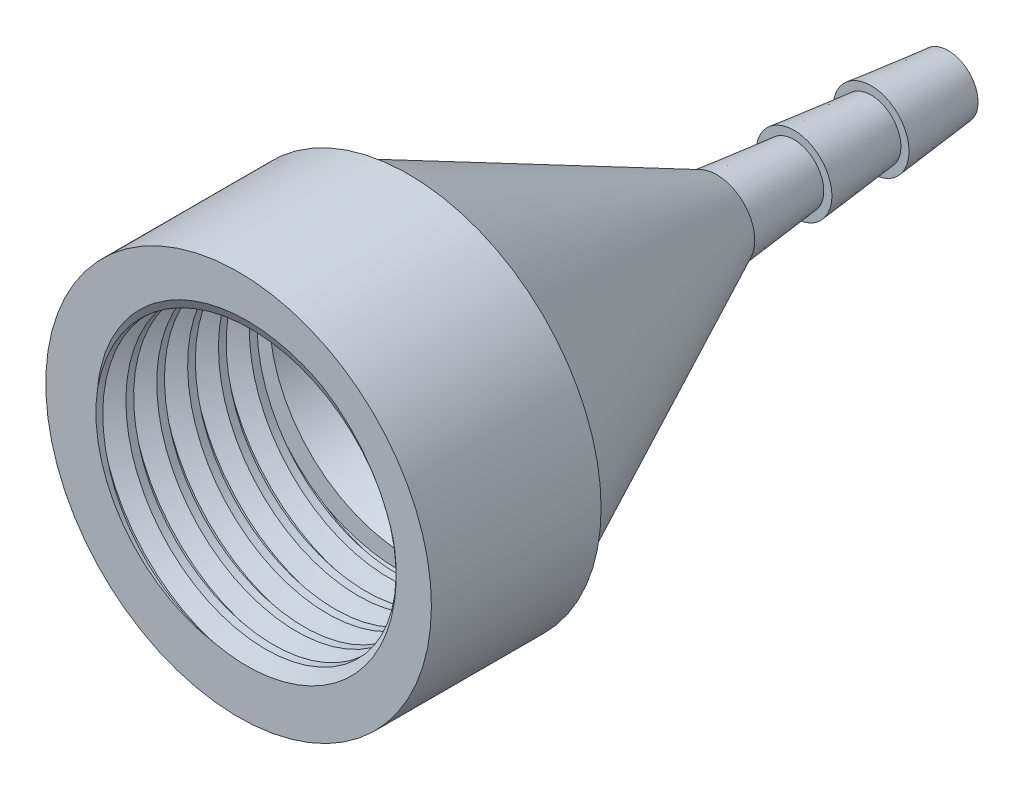
SolidWorks part; units mm, degrees
ref_plane "Front Plane" through (0, 0, 0) normal (0, 0, 1) x (1, 0, 0)
ref_plane "Top Plane" through (0, 0, 0) normal (0, 1, 0) x (1, 0, 0)
ref_plane "Right Plane" through (0, 0, 0) normal (1, 0, 0) x (0, 0, -1)
sketch "Sketch1" plane through (0, 0, 0) normal (0, 0, 1) x (1, 0, 0)
  circle A0 centre (0, 0) radius 12.5
  circle A1 centre (0, 0) radius 9.25
  dimension "D1" = 25
  dimension "D2" = 18.5
extrude "Boss-Extrude1" add sketch "Sketch1" along normal blind 11
thread "Thread1" pitch 2 method cut profile "Thread Profile1" start angle 0, offset 1.55, length 0, pitch 2, diameter 18.5
ref_plane "Plane1" through (-9.25, 0, 12.55) normal (0, -1, 0) x (-1, 0, 0)
sketch "Thread Profile1" plane through (-9.25, 0, 12.55) normal (0, -1, 0) x (-1, 0, 0)
  line L0 (0, 0) -> (0, 2) construction
  line L1 (0, 0) -> (1.0825, 0.625)
  line L2 (1.0825, 0.625) -> (1.0825, 0.875)
  line L3 (1.0825, 0.875) -> (0, 1.5)
  line L4 (1.0825, 0.75) -> (0, 0.75) construction
  line L11 (0, 0) -> (0, 1.5)
  point P2 (0, 0)
  dimension "Pitch" = 2
  dimension "Profile_Angle" = 60
  dimension "Profile_Land" = 0.25
  dimension "Profile_Height" = 1.0825
sketch "Sketch6" plane through (0, 0, 0) normal (0, 0, 1) x (1, 0, 0)
  circle A0 centre (0, 0) radius 12
extrude "Boss-Extrude2" add sketch "Sketch6" against normal blind 20 draft 25.5 separate body
sketch "Sketch13" plane through (0, 0, 0) normal (0, 0, -1) x (-1, 0, 0)
  circle A0 centre (0, 0) radius 9
extrude "Cut-Extrude1" cut sketch "Sketch13" along normal blind 20 draft 21.5
sketch "Sketch18" plane through (0, 0, -20) normal (0, 0, -1) x (-1, 0, 0)
  circle A0 centre (0, 0) radius 2.46
  dimension "D1" = 4.92
extrude "Boss-Extrude3" add sketch "Sketch18" along normal blind 5 draft 6
pattern_linear "LPattern1" count 3 spacing 5 along (0, 0, -1) of "Boss-Extrude3"
sketch "Sketch20" plane through (0, 0, -35) normal (0, 0, -1) x (-1, 0, 0)
  circle A0 centre (0, 0) radius 1
  dimension "D1" = 2
extrude "Cut-Extrude2" cut sketch "Sketch20" against normal through all
fillet "Fillet1" radius 10 1 edges at (-1, 0, -20)
